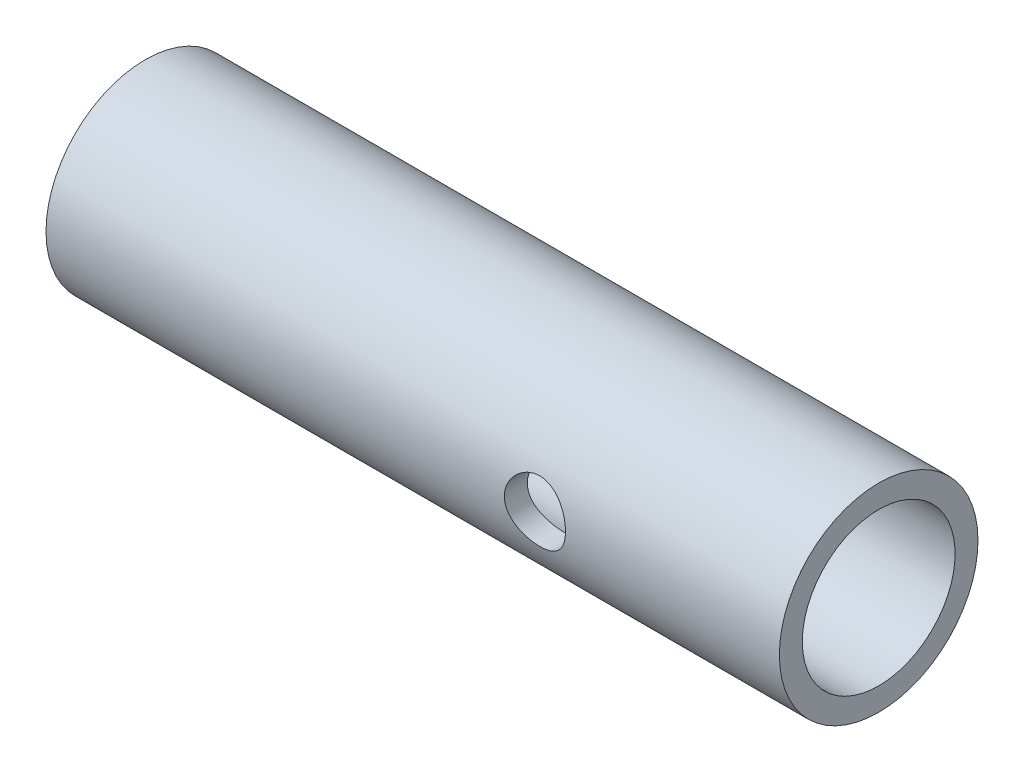
SolidWorks part; units mm, degrees
ref_plane "Front Plane" through (0, 0, 0) normal (0, 0, 1) x (1, 0, 0)
ref_plane "Top Plane" through (0, 0, 0) normal (0, 1, 0) x (1, 0, 0)
ref_plane "Right Plane" through (0, 0, 0) normal (1, 0, 0) x (0, 0, -1)
sketch "Sketch1" plane through (0, 0, 0) normal (0, 0, 1) x (1, 0, 0)
  line L0 (0, 15.875) -> (152.4, 15.875)
  line L1 (152.4, 15.875) -> (152.4, 20.6375)
  line L2 (152.4, 20.6375) -> (0, 20.6375)
  line L3 (0, 20.6375) -> (0, 15.875)
  line L4 (0, 0) -> (171.2829, 0) construction
  point P5 (0, 0)
  dimension "D1" = 31.75
  dimension "D2" = 4.7625
  dimension "D3" = 152.4
revolve "Revolve1" add sketch "Sketch1" angle 360 about L4
sketch "Sketch2" plane through (0, 0, 0) normal (0, 0, 1) x (1, 0, 0)
  line L0 (152.4, -15.875) -> (152.4, 15.875) construction
  line L1 (101.6, 0) -> (0, 0) construction
  circle A0 centre (101.6, 0) radius 6.35
  dimension "D1" = 12.7
  dimension "D2" = 50.8
extrude "Cut-Extrude1" cut sketch "Sketch2" against normal through all and the other way through all
